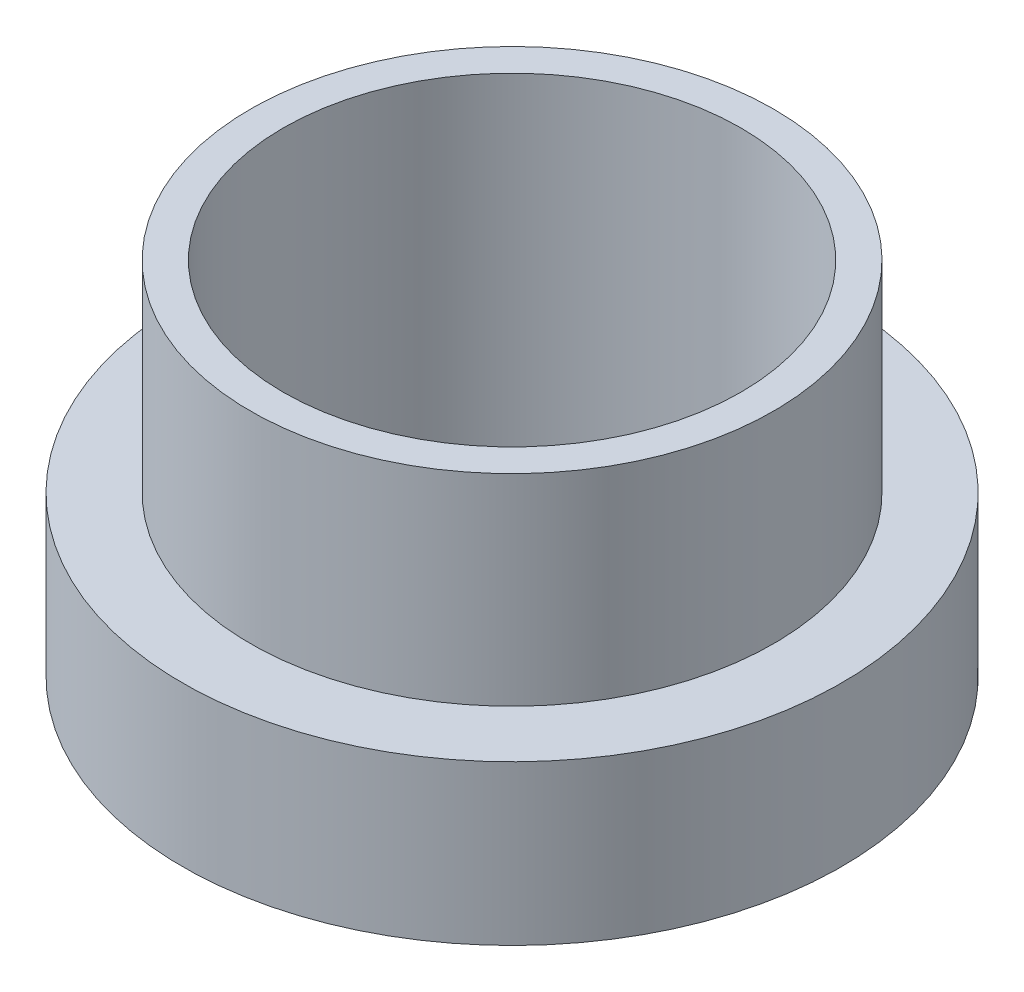
SolidWorks part; units mm, degrees
material "AISI 4130 Steel, normalized at 870C"
ref_plane "Front Plane" through (0, 0, 0) normal (0, 0, 1) x (1, 0, 0)
ref_plane "Top Plane" through (0, 0, 0) normal (0, 1, 0) x (1, 0, 0)
ref_plane "Right Plane" through (0, 0, 0) normal (1, 0, 0) x (0, 0, -1)
sketch "Sketch1" plane through (0, 0, 0) normal (0, 1, 0) x (1, 0, 0)
  circle A0 centre (0, 0) radius 5.5562
  circle A1 centre (0, 0) radius 8
  dimension "D1" = 11.1125
  dimension "D2" = 16
extrude "Boss-Extrude1" add sketch "Sketch1" along normal blind 3.8626
sketch "Sketch2" plane through (0, 3.8626, 0) normal (0, 1, 0) x (1, 0, 0)
  circle A1 centre (0, 0) radius 5.5562
  circle A2 centre (0, 0) radius 6.35
  circle A3 centre (0, 0) radius 5.5562 construction
  dimension "D1" = 12.7
extrude "Boss-Extrude2" add sketch "Sketch2" along normal blind 4.89
move or copy body "Body-Move/Copy1" [suppressed] bodies to move or copy 101
